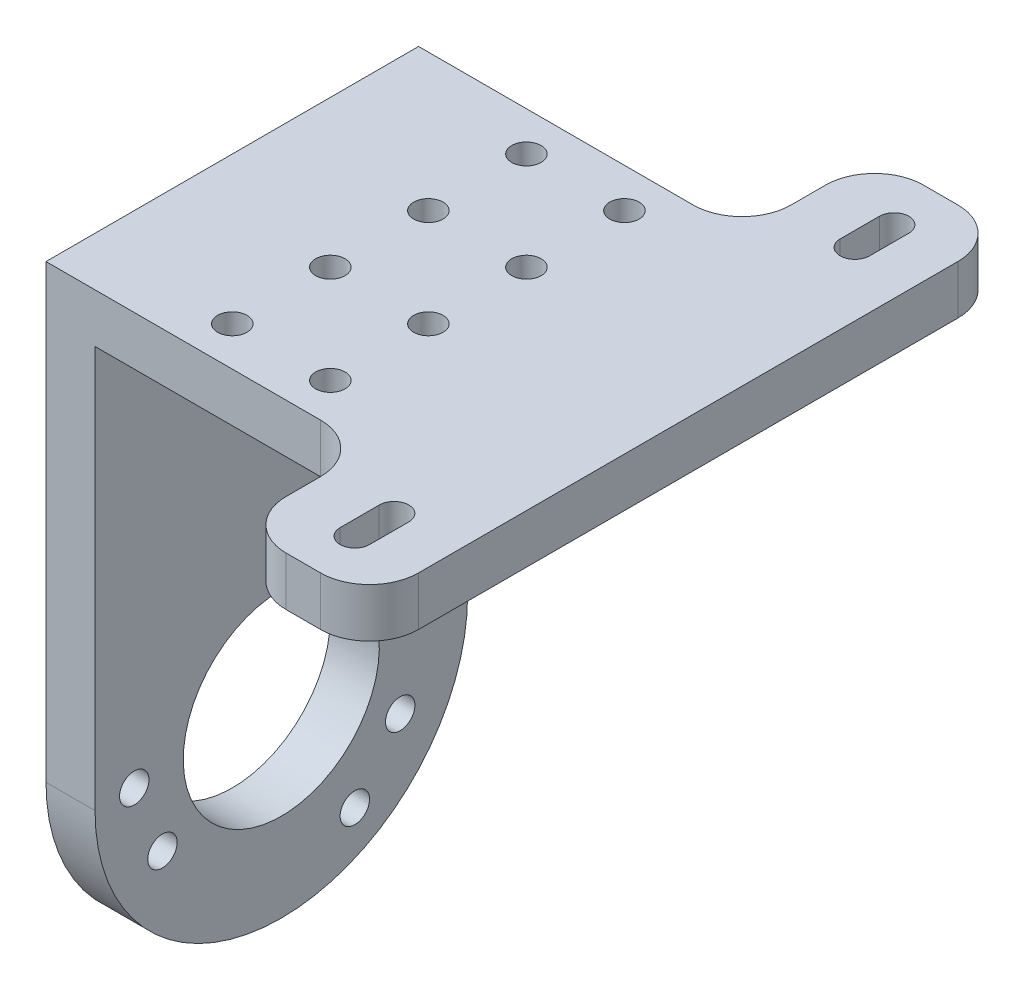
SolidWorks part; units mm, degrees
material "ABS"
ref_plane "Спереди" through (0, 0, 0) normal (0, 0, 1) x (1, 0, 0)
ref_plane "Сверху" through (0, 0, 0) normal (0, 1, 0) x (1, 0, 0)
ref_plane "Справа" through (0, 0, 0) normal (1, 0, 0) x (0, 0, -1)
sketch "Эскиз1" plane through (0, 0, 0) normal (0, 0, 1) x (1, 0, 0)
  line L0 (0, 0) -> (5, 0)
  line L1 (5, 0) -> (5, 41)
  line L2 (0, 0) -> (0, 46)
  line L3 (0, 0) -> (0, -19)
  line L4 (0, -19) -> (5, -19)
  line L5 (5, -19) -> (5, 0)
  line L6 (0, 46) -> (46.5, 46)
  line L7 (46.5, 46) -> (46.5, 41)
  line L8 (46.5, 41) -> (5, 41)
  dimension "D1" = 5
  dimension "D2" = 19
  dimension "D3" = 41
  dimension "D4" = 46.5
  dimension "D5" = 5
extrude "Бобышка-Вытянуть1" add sketch "Эскиз1" along normal blind 32.5 and the other way blind 32.5 contours L8 L7 L6 L2 L0 L1 | L4 L5 L0 L3 region at (0.6541, 23, 0) region at (2.5, -9.5, 0)
sketch "Эскиз2" plane through (5, 0, 0) normal (1, 0, 0) x (0, 0, -1)
  circle A0 centre (0, 0) radius 10
extrude "Вырез-Вытянуть1" cut sketch "Эскиз2" against normal blind 19
sketch "Эскиз3" plane through (5, 0, 0) normal (1, 0, 0) x (0, 0, -1)
  line L0 (0, 0) -> (0, 22.9379) construction
  line L1 (0, 0) -> (-23.6775, 0) construction
  line L2 (0, 0) -> (7.5, 12.9904) construction
  circle A0 centre (0, 0) radius 14 construction
  circle A1 centre (0, 0) radius 15 construction
  circle A2 centre (0, 14) radius 1.5
  circle A4 centre (7.5, 12.9904) radius 1.5
  circle A5 centre (12.1244, -7) radius 1.5
  circle A6 centre (7.5, -12.9904) radius 1.5
  circle A7 centre (-12.1244, -7) radius 1.5
  circle A8 centre (-15, 0) radius 1.5
  point P23 (0, 0)
  dimension "D1" = 3
extrude "Вырез-Вытянуть2" cut sketch "Эскиз3" against normal through all
sketch "Эскиз4" plane through (0, 46, 0) normal (0, 1, 0) x (1, 0, 0)
  line L0 (0, 0) -> (25, 0) construction
  line L1 (0, 0) -> (15, 0) construction
  line L2 (15, 0) -> (15, 15) construction
  line L3 (25, 0) -> (25, 15) construction
  line L4 (0, 0) -> (40, 0) construction
  line L5 (40, 0) -> (40, 25) construction
  line L6 (38.5, 27.5) -> (38.5, 23.5)
  line L7 (40, 0) -> (40, -25) construction
  line L8 (41.5, 23.5) -> (41.5, 27.5)
  line L9 (38.5, -23.5114) -> (38.5, -27.5164)
  line L10 (41.5, -27.5) -> (41.5, -23.4886)
  circle A0 centre (15, 15) radius 1.5
  circle A1 centre (15, 5) radius 1.5
  circle A2 centre (25, 5) radius 1.5
  circle A3 centre (25, 15) radius 1.5
  circle A4 centre (25, -15) radius 1.5
  circle A5 centre (25, -5) radius 1.5
  circle A6 centre (15, -5) radius 1.5
  circle A7 centre (15, -15) radius 1.5
  arc A10 (41.5, 27.5) -> (38.5, 27.5) centre (40, 27.5) ccw
  arc A11 (38.5, 23.5) -> (41.5, 23.5) centre (40, 23.5) ccw
  arc A12 (41.5, -23.4886) -> (38.5, -23.5114) centre (40, -23.5) ccw
  arc A13 (38.5, -27.5164) -> (41.5, -27.5) centre (40, -27.5) ccw
  dimension "D3" = 15
  dimension "D4" = 5
  dimension "D5" = 40
  dimension "D8" = 2.5
  dimension "D12" = 1.5
  dimension "D1" = 25
  dimension "D2" = 15
  dimension "D6" = 25
  dimension "D7" = 25
  dimension "D9" = 2.5
  dimension "D10" = 1.5
  dimension "D11" = 1.5
  dimension "D13" = 3
extrude "Вырез-Вытянуть3" cut sketch "Эскиз4" against normal through all
sketch "Эскиз5" plane through (0, 0, 0) normal (-1, 0, 0) x (0, 0, 1)
  line L0 (-19, 0) -> (-19, 40)
  line L1 (-19, 40) -> (-39.0972, 40)
  line L2 (19, 0) -> (19, 40)
  line L3 (19, 40) -> (42.0169, 40)
  line L4 (42.0169, 40) -> (42.0169, -21.2814)
  line L5 (42.0169, -21.2814) -> (-39.0972, -21.2814)
  line L6 (-39.0972, -21.2814) -> (-39.0972, 40)
  circle A1 centre (0, 0) radius 19
  line M9 (-32.5, -19) -> (32.5, -19)
  line M10 (32.5, -19) -> (32.5, 46)
  line M12 (-32.5, 46) -> (-32.5, -19)
  dimension "D1" = 38
  dimension "D2" = 40
  dimension "D3" = 40
extrude "Вырез-Вытянуть4" cut sketch "Эскиз5" against normal through all both and the other way through all contours A1 L0 L1 M12 M9 | A1 L3 L2 M9 M10 | L6 L5 L4 L3 L1 M10 M9 M12 region at (0, 8.2612, -24.7755) region at (0, 8.2612, 24.7755) region at (0, -20.0166, 16.25)
sketch "Эскиз6" plane through (0, 46, 0) normal (0, 1, 0) x (1, 0, 0)
  line L0 (0, 19) -> (33, 19)
  line L1 (33, 19) -> (33, 32.5)
  line L2 (0, 32.5) -> (46.5, 32.5) construction
  line L3 (33, 32.5) -> (0, 32.5)
  line L4 (0, 32.5) -> (0, 19)
  line L5 (0, 0) -> (-7.3091, 0) construction
  line L6 (0, -32.5) -> (0, -19)
  line L7 (33, -32.5) -> (0, -32.5)
  line L8 (33, -19) -> (33, -32.5)
  line L9 (0, -19) -> (33, -19)
extrude "Вырез-Вытянуть5" cut sketch "Эскиз6" against normal blind 10
fillet "Скругление3" radius 5 6 edges at (46.5, 43.5, -32.5) (33, 43.5, -32.5) (33, 43.5, -19) (46.5, 43.5, 32.5) (33, 43.5, 32.5) (33, 43.5, 19)
